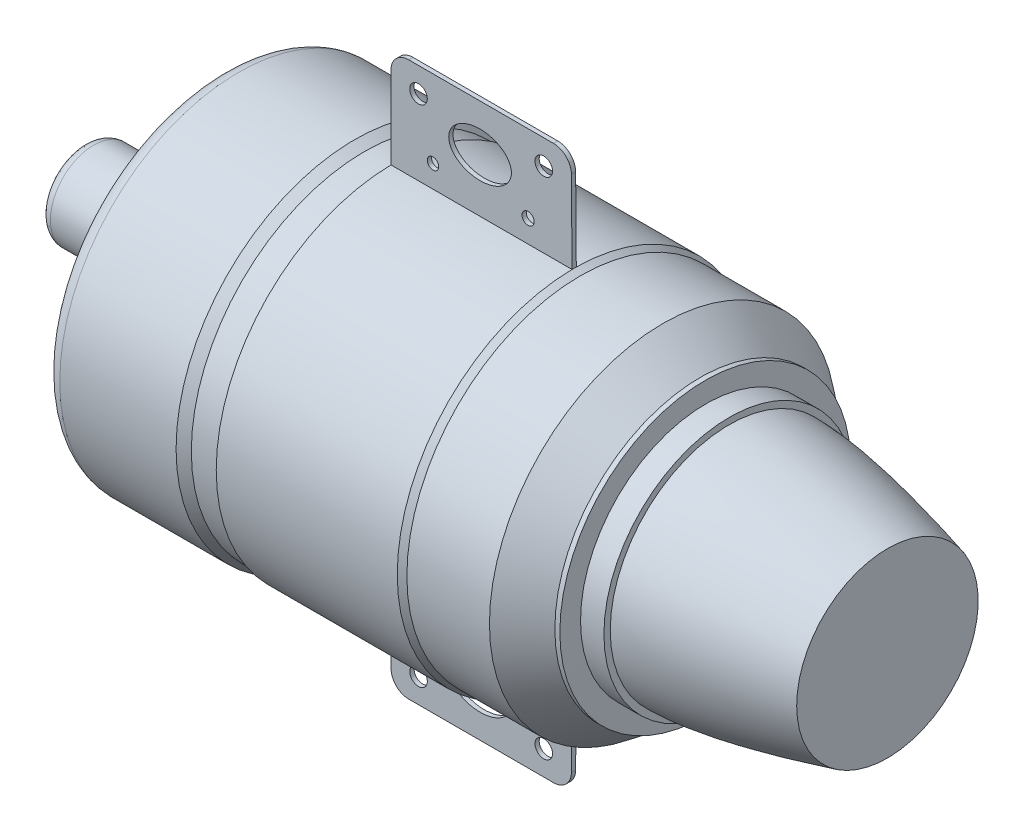
SolidWorks part; units mm, degrees
ref_plane "Front Plane" through (0, 0, 0) normal (0, 0, 1) x (1, 0, 0)
ref_plane "Top Plane" through (0, 0, 0) normal (0, 1, 0) x (1, 0, 0)
ref_plane "Right Plane" through (0, 0, 0) normal (1, 0, 0) x (0, 0, -1)
sketch "Sketch1" plane through (0, 0, 0) normal (0, 0, 1) x (1, 0, 0)
  line L0 (-26.7963, 0) -> (12.4273, 0) construction
  line L1 (1.0905, 5.1722) -> (9.4504, 5.1722)
  line L2 (9.4504, 5.1722) -> (9.4504, 0)
  line L3 (17.0937, 0) -> (17.0937, 18.9133)
  line L4 (19.2083, 21.3115) -> (33.0854, 21.3115)
  line L5 (33.0854, 21.3115) -> (34.2496, 20.6596)
  line L6 (34.2496, 20.6596) -> (37.6708, 20.6596)
  line L7 (59.2694, 21.1075) -> (60.0052, 20.6955)
  line L8 (60.0052, 20.6955) -> (69.8575, 20.6955)
  line L9 (69.8575, 20.6955) -> (74.3124, 17.3492)
  line L10 (74.3124, 17.3492) -> (74.9094, 17.3492)
  line L11 (74.9094, 17.3492) -> (74.9817, 14.9528)
  line L12 (74.9817, 14.9528) -> (77.7707, 14.9528)
  line L13 (77.7707, 14.9528) -> (77.7707, 14.1977)
  line L14 (96.6452, 0) -> (96.6452, 10.8275)
  line L15 (85.173, 14.1977) -> (70.5882, 14.1977) construction
  line L16 (0, 0) -> (0, -2.4925) construction
  line L17 (37.6708, 20.6596) -> (37.6708, 21.1075)
  line L18 (37.6708, 21.1075) -> (59.2694, 21.1075)
  line L19 (17.0937, 17.7576) -> (11.0147, 6.1199)
  line L20 (17.0937, 14.4568) -> (12.1234, 4.9415)
  line L21 (12.1234, 4.9415) -> (12.1234, 0)
  line L22 (37.6708, 21.1075) -> (37.6708, 30.916)
  line L23 (17.0937, 0) -> (96.6452, 0)
  line L24 (39.7842, 33.0294) -> (57.0627, 33.0294)
  line L25 (9.4504, 0) -> (0, 0)
  line L26 (59.1927, 30.916) -> (59.2694, 21.1075)
  line L27 (12.1234, 0) -> (9.4504, 0)
  line L28 (9.4504, 5.1722) -> (9.4504, 7.9511)
  line L29 (9.4504, 7.9511) -> (11.9713, 7.9511)
  line L30 (59.2694, 21.1075) -> (59.2694, 18.6791)
  line L31 (59.2694, 18.6791) -> (37.6708, 18.6791)
  line L32 (37.6708, 18.6791) -> (37.6708, 20.6596)
  arc A0 (17.0937, 18.9133) -> (19.2083, 21.3115) centre (19.511, 18.9133) cw
  arc A1 (0, 0) -> (1.0905, 5.1722) centre (12.8113, 0) cw
  arc A2 (9.4504, 5.1722) -> (11.0147, 6.1199) centre (9.4504, 6.9371) ccw
  arc A3 (37.6708, 30.916) -> (39.7842, 33.0294) centre (39.7842, 30.916) cw
  arc A4 (57.0627, 33.0294) -> (59.1927, 30.916) centre (57.0627, 30.8993) cw
  circle A5 centre (55.9165, 30.1262) radius 0.9796
  circle A6 centre (40.8958, 30.1262) radius 0.98
  circle A7 centre (42.6827, 23.7624) radius 0.6813
  circle A8 centre (54.0254, 23.7624) radius 0.7233
  ellipse E0 centre (48.297, 27.463) end of major axis (52.0357, 27.463) minor radius 2.6632
  spline S0 degree 2 poles (77.7707, 14.1977) (83.9678, 14.1977) (96.6452, 10.8275) knots 0 0 0 1 1 1
revolve "Revolve1" add sketch "Sketch1" angle 360 about L0 region at (4.898, 2.5349, 0) region at (53.424, 9.3335, 0) region at (48.4701, 19.8933, 0)
extrude "Boss-Extrude1" add sketch "Sketch1<4>" along normal mid plane 0.508 contours A4 L24 A3 L22 L18 L26 E0 A8 A7 A6 A5 | L32 L31 L30 L18 L17 | A6 | A5 region at (48.4701, 19.8933, 0) region at (37.9175, 26.0118, 0)
sketch "Sketch1<4>" plane through (0, 0, 0) normal (0, 0, 1) x (1, 0, 0) same geometry as "Sketch1"
extrude "Boss-Extrude2" add sketch "Sketch1<5>" along normal mid plane 2.54 contours A2 L2 L27 L21 L20 L3 L19 region at (12.7514, 7.2447, 0)
sketch "Sketch1<5>" plane through (0, 0, 0) normal (0, 0, 1) x (1, 0, 0) same geometry as "Sketch1"
revolve "Cut-Revolve1" cut sketch "Sketch1<6>" angle 360 about L0 region at (10.3968, 6.8036, 0)
sketch "Sketch1<6>" plane through (0, 0, 0) normal (0, 0, 1) x (1, 0, 0) same geometry as "Sketch1"
pattern_circular "CirPattern1" count 4 over 360 about axis through (-26.7963, 0, 0) along (1, 0, 0) of "Boss-Extrude2", "Cut-Revolve1"
mirror "Mirror1" about plane through (0, 0, 0) normal (0, 1, 0) of "Boss-Extrude1"
fillet "Fillet1" radius 1.27 1 edges at (1.0905, 0, 5.1722)
scale "Scale1" scale about centroid uniform scaling yes scale factor 2.276
sketch "Sketch2" plane through (0, 0, 0.5781) normal (0, 0, 1) x (1, 0, 0)
  line L0 (46.4059, 75.1749) -> (46.4059, 62.3363) construction
  line L1 (0, 0) -> (39.7086, 0)
  line L5 (21.9329, 70.3648) -> (21.9329, 48.0373)
  line L6 (21.9329, 48.0373) -> (71.0914, 48.0373)
  line L7 (71.0914, 48.0373) -> (71.0914, 48.0407)
  line L8 (71.0914, 48.0407) -> (70.9167, 70.3648)
  line L9 (66.0688, 75.1749) -> (26.743, 75.1749)
  line L14 (66.0688, 75.1749) -> (26.743, 75.1749)
  circle A0 centre (29.4059, 68.5) radius 2.3812
  circle A1 centre (63.4059, 68.5) radius 2.3812
  arc A2 (70.9167, 70.3648) -> (66.0688, 75.1749) centre (66.0688, 70.3269) ccw
  arc A3 (26.743, 75.1749) -> (21.9329, 70.3648) centre (26.743, 70.3648) ccw
  arc A4 (70.9167, 70.3648) -> (66.0688, 75.1749) centre (66.0688, 70.3269) ccw
  arc A5 (26.743, 75.1749) -> (21.9329, 70.3648) centre (26.743, 70.3648) ccw
  circle A6 centre (29.4059, -68.5) radius 2.3812
  circle A7 centre (63.4059, -68.5) radius 2.3812
  dimension "D2" = 4.7625
  dimension "D3" = 34
  dimension "D4" = 17
  dimension "D5" = 137
  dimension "D6" = 68.5
  dimension "D1" = 0
extrude "Cut-Extrude1" cut sketch "Sketch2" against normal through all contours A0 | A1 | A6 | A7 region at (29.4059, 68.5, 0.5781) region at (63.4059, 68.5, 0.5781) region at (29.4059, -68.5, 0.5781) region at (63.4059, -68.5, 0.5781)
ref_axis "Centeral Axis" through (-74.8041, 0, 0) along (1, 0, 0)
ref_plane "Middle length plane" through (46.6991, 0.1828, 0) normal (-1, -0.0039, 0) x (0, 0, 1)
ref_point "Turbine centroid"
equation "\"D4@Sketch2\"=\"D3@Sketch2\"/2"
equation "\"D6@Sketch2\"=\"D5@Sketch2\"/2"
equation "\"D2@Sketch2\"=6/32"
